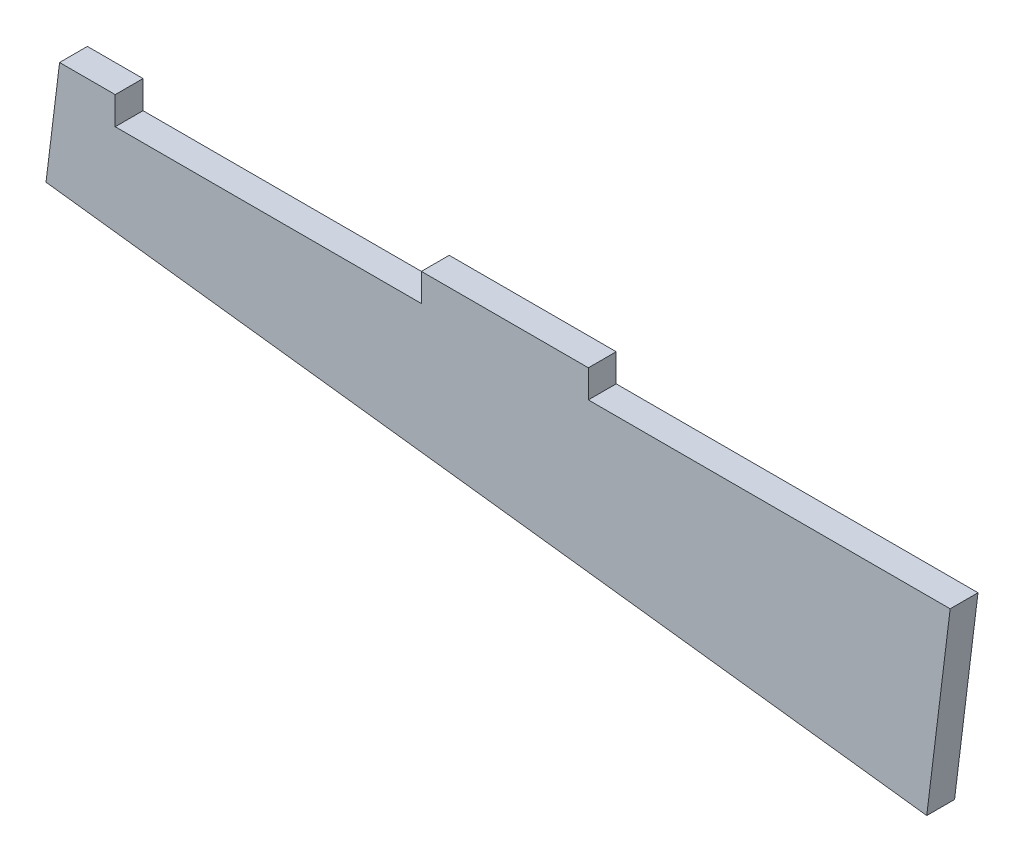
SolidWorks part; units mm, degrees
ref_plane "Front Plane" through (0, 0, 0) normal (0, 0, 1) x (1, 0, 0)
ref_plane "Top Plane" through (0, 0, 0) normal (0, 1, 0) x (1, 0, 0)
ref_plane "Right Plane" through (0, 0, 0) normal (1, 0, 0) x (0, 0, -1)
sketch "Sketch1" plane through (0, 0, 0) normal (0, 0, 1) x (1, 0, 0)
  line L0 (-195.3168, -62.6592) -> (-182.6168, -62.6592)
  line L4 (-182.6168, -62.6592) -> (-182.6168, -69.0092)
  line L5 (-182.6168, -69.0092) -> (-112.7668, -69.0092)
  line L6 (-112.7668, -69.0092) -> (-112.7668, -62.6592)
  line L7 (-112.7668, -62.6592) -> (-74.6668, -62.6592)
  line L8 (-74.6668, -62.6592) -> (-74.6668, -69.0092)
  line L9 (-74.6668, -69.0092) -> (7.8832, -69.0092)
  line L10 (7.8832, -69.0092) -> (2.5379, -112.5435)
  line L11 (2.5379, -112.5435) -> (-198.4122, -87.8699)
  line L12 (-198.4122, -87.8699) -> (-195.3168, -62.6592)
  line L13 (-378.8613, -54.018) -> (14.8387, -102.3583) construction
  dimension "D1" = 12.7
  dimension "D2" = 6.35
  dimension "D3" = 69.85
  dimension "D4" = 38.1
  dimension "D5" = 82.55
  dimension "D6" = 25.4
extrude "Boss-Extrude1" add sketch "Sketch1" against normal blind 6.35
